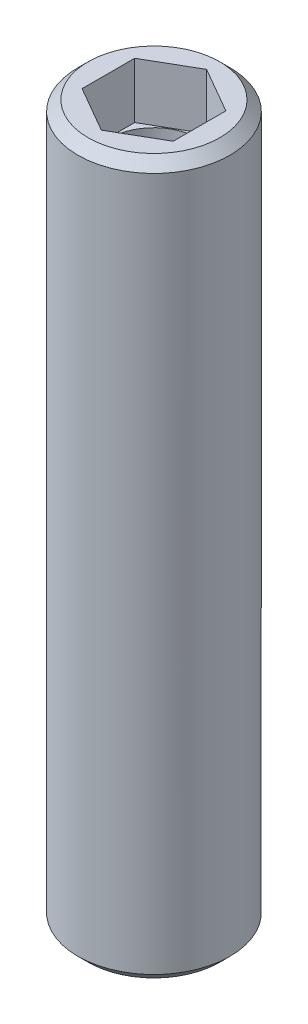
SolidWorks part; units mm, degrees
ref_plane "Front Plane" through (0, 0, 0) normal (0, 0, 1) x (1, 0, 0)
ref_plane "Top Plane" through (0, 0, 0) normal (0, 1, 0) x (1, 0, 0)
ref_plane "Right Plane" through (0, 0, 0) normal (1, 0, 0) x (0, 0, -1)
sketch "Sketch1" plane through (0, 0, 0) normal (0, 1, 0) x (1, 0, 0)
  line L1 (0, 13.1982) -> (-11.43, 6.5991)
  line L2 (-11.43, 6.5991) -> (-11.43, -6.5991)
  line L3 (-11.43, -6.5991) -> (0, -13.1982)
  line L4 (0, -13.1982) -> (11.43, -6.5991)
  line L5 (11.43, -6.5991) -> (11.43, 6.5991)
  line L6 (11.43, 6.5991) -> (0, 13.1982)
  circle A0 centre (0, 0) radius 11.43 construction
  circle A1 centre (0, 0) radius 19.05
  dimension "D1" = 22.86
  dimension "D2" = 38.1
extrude "Boss-Extrude1" add sketch "Sketch1" against normal blind 13.97
sketch "Sketch2" plane through (0, -13.97, 0) normal (0, -1, 0) x (1, 0, 0)
  circle A1 centre (0, 0) radius 11.176
  circle A2 centre (0, 0) radius 19.05 construction
  circle A3 centre (0, 0) radius 19.05
  dimension "D1" = 22.352
extrude "Boss-Extrude2" add sketch "Sketch2" along normal blind 165.1
ref_plane "Plane1" through (0, -323.85, 0) normal (0, -1, 0) x (-1, 0, 0)
sketch "Sketch4" plane through (0, -323.85, 0) normal (0, -1, 0) x (-1, 0, 0)
  circle A0 centre (0, 0) radius 25.4051
  circle A1 centre (0, 0) radius 16.6549
chamfer "Chamfer1" distance 2.54 angle 45 2 edges at (0, -179.07, -19.05) (0, 0, 19.05)
sketch "Sketch7" plane through (0, 0, 0) normal (1, 0, 0) x (0, 0, -1)
  line L0 (0, -2.54) -> (0, -176.53) construction
  line L1 (-19.05, -2.54) -> (19.05, -2.54) construction
  line L2 (19.05, -176.53) -> (-19.05, -176.53) construction
  text T0 "TRANSDUCER WRENCH" font "Century Gothic" height in points 18
extrude "Cut-Extrude1" cut sketch "Sketch7" along normal offset from surface (16.51 mm away) 2.54 from offset 33.02
